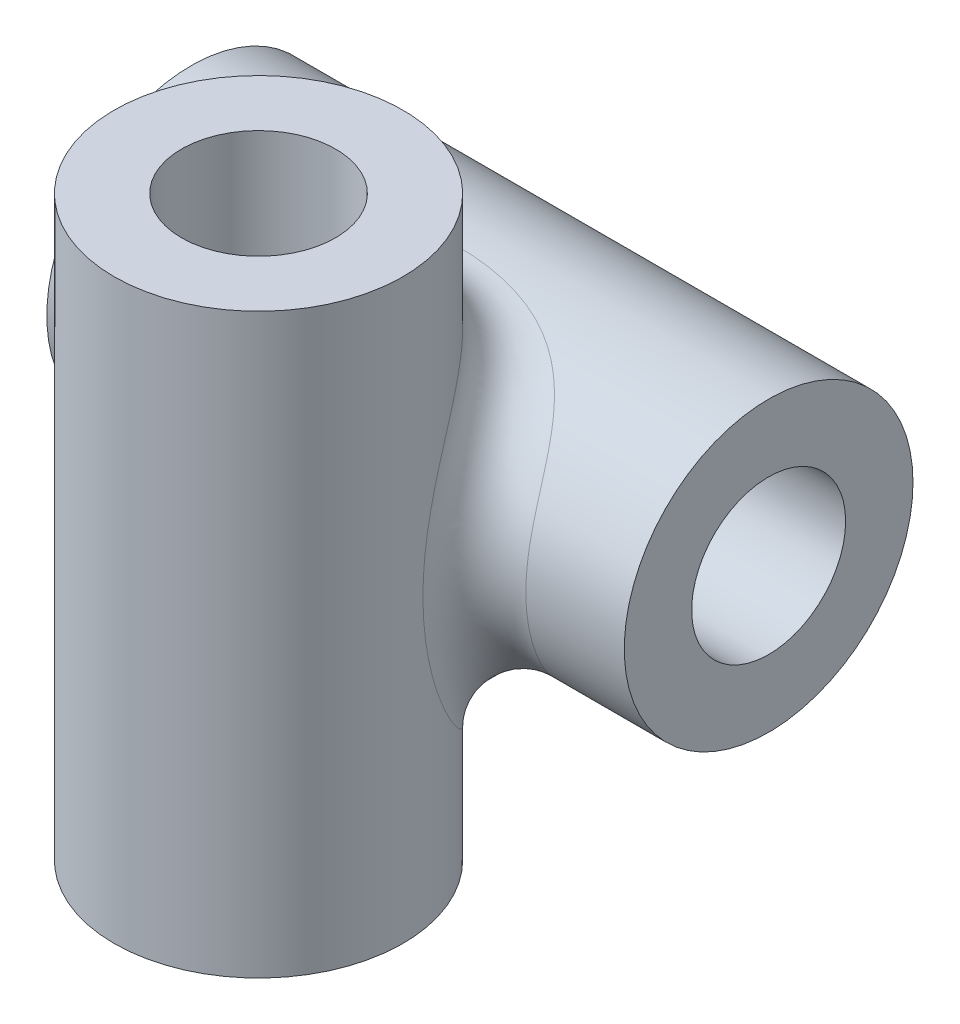
SolidWorks part; units mm, degrees
ref_plane "Front Plane" through (0, 0, 0) normal (0, 0, 1) x (1, 0, 0)
ref_plane "Top Plane" through (0, 0, 0) normal (0, 1, 0) x (1, 0, 0)
ref_plane "Right Plane" through (0, 0, 0) normal (1, 0, 0) x (0, 0, -1)
sketch "Sketch2" plane through (0, 0, 0) normal (0, 1, 0) x (1, 0, 0)
  circle A0 centre (0, 0) radius 8
  circle A1 centre (0, 0) radius 15
  dimension "D1" = 30
  dimension "D2" = 16
extrude "Boss-Extrude2" add sketch "Sketch2" along normal mid plane 60
sketch "Sketch3" plane through (0, 0, 0) normal (1, 0, 0) x (0, 0, -1)
  circle A0 centre (23, 0) radius 8
  circle A1 centre (23, 0) radius 15
  dimension "D1" = 30
  dimension "D2" = 16
  dimension "D3" = 23
extrude "Boss-Extrude3" add sketch "Sketch3" along normal mid plane 60
fillet "Fillet1" radius 5 1 edges at (-3.3823, -12.4366, -14.6137)
